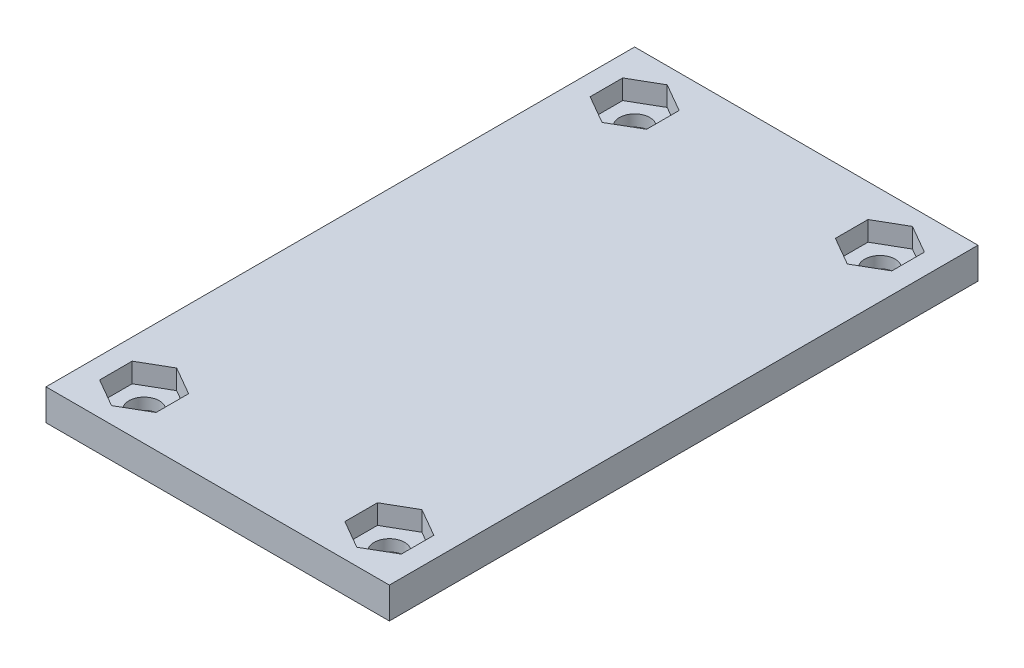
SolidWorks part; units mm, degrees
ref_plane "Front Plane" through (0, 0, 0) normal (0, 0, 1) x (1, 0, 0)
ref_plane "Top Plane" through (0, 0, 0) normal (0, 1, 0) x (1, 0, 0)
ref_plane "Right Plane" through (0, 0, 0) normal (1, 0, 0) x (0, 0, -1)
sketch "Sketch1" plane through (0, 0, 0) normal (0, 1, 0) x (1, 0, 0)
  line L1 (-12.5, -25) -> (12.5, -25) construction
  line L2 (-12.5, -25) -> (-12.5, 25) construction
  line L3 (-12.5, 25) -> (12.5, 25) construction
  line L4 (12.5, -25) -> (12.5, 25) construction
  line L5 (-12.5, -25) -> (12.5, 25) construction
  line L6 (-12.5, 25) -> (12.5, -25) construction
  line L7 (-17.5, -30) -> (17.5, -30)
  line L8 (-17.5, -30) -> (-17.5, 30)
  line L9 (-17.5, 30) -> (17.5, 30)
  line L10 (17.5, -30) -> (17.5, 30)
  line L11 (-17.5, -30) -> (17.5, 30) construction
  line L12 (-17.5, 30) -> (17.5, -30) construction
  line L13 (-12.5, 28.3198) -> (-15.375, 26.6599)
  line L14 (-15.375, 26.6599) -> (-15.375, 23.3401)
  line L15 (-15.375, 23.3401) -> (-12.5, 21.6802)
  line L16 (-12.5, 21.6802) -> (-9.625, 23.3401)
  line L17 (-9.625, 23.3401) -> (-9.625, 26.6599)
  line L18 (-9.625, 26.6599) -> (-12.5, 28.3198)
  line L19 (12.5, 28.3198) -> (9.625, 26.6599)
  line L20 (9.625, 26.6599) -> (9.625, 23.3401)
  line L21 (9.625, 23.3401) -> (12.5, 21.6802)
  line L22 (12.5, 21.6802) -> (15.375, 23.3401)
  line L23 (15.375, 23.3401) -> (15.375, 26.6599)
  line L24 (15.375, 26.6599) -> (12.5, 28.3198)
  line L25 (-12.5, -28.3198) -> (-9.625, -26.6599)
  line L26 (-9.625, -26.6599) -> (-9.625, -23.3401)
  line L27 (-9.625, -23.3401) -> (-12.5, -21.6802)
  line L28 (-12.5, -21.6802) -> (-15.375, -23.3401)
  line L29 (-15.375, -23.3401) -> (-15.375, -26.6599)
  line L30 (-15.375, -26.6599) -> (-12.5, -28.3198)
  line L31 (12.5, -21.6802) -> (9.625, -23.3401)
  line L32 (9.625, -23.3401) -> (9.625, -26.6599)
  line L33 (9.625, -26.6599) -> (12.5, -28.3198)
  line L34 (12.5, -28.3198) -> (15.375, -26.6599)
  line L35 (15.375, -26.6599) -> (15.375, -23.3401)
  line L36 (15.375, -23.3401) -> (12.5, -21.6802)
  circle A0 centre (-12.5, 25) radius 1.55
  circle A1 centre (12.5, 25) radius 1.55
  circle A2 centre (-12.5, -25) radius 1.55
  circle A3 centre (12.5, -25) radius 1.55
  circle A4 centre (-12.5, 25) radius 2.875 construction
  circle A5 centre (12.5, 25) radius 2.875 construction
  circle A6 centre (-12.5, -25) radius 2.875 construction
  circle A7 centre (12.5, -25) radius 2.875 construction
  point P0 (0, 0)
  point P10 (0, 0)
  dimension "D3" = 3.1
  dimension "D6" = 5.75
  dimension "D1" = 50
  dimension "D2" = 25
  dimension "D4" = 60
  dimension "D5" = 35
extrude "Boss-Extrude1" add sketch "Sketch1" along normal blind 3.175 contours L7 L10 L9 L8 L36 L35 L34 L33 L32 L31 L30 L29 L28 L27 L26 L25 L24 L23 L22 L21 L20 L19 L18 L17 L16 L15 L14 L13 | L17 L18 L13 L14 L15 L16 A0 | L23 L24 L19 L20 L21 L22 A1 | L35 L36 L31 L32 L33 L34 A3 | L29 L30 L25 L26 L27 L28 A2 region at (0, 0, 0) region at (-11.1064, 0, -27.4138) region at (13.8936, 0, -27.4138) region at (-13.8936, 0, 27.4138) region at (13.8936, 0, 22.5862)
extrude "Cut-Extrude1" cut sketch "Sketch1<3>" against normal blind 2 from surface contours L29 L30 L25 L26 L27 L28 A2 | L17 L18 L13 L14 L15 L16 A0 | L23 L24 L19 L20 L21 L22 A1 | L35 L36 L31 L32 L33 L34 A3 region at (-11.1064, 0, -27.4138) region at (13.8936, 0, -27.4138) region at (-13.8936, 0, 27.4138) region at (13.8936, 0, 22.5862) starting at face at (0, 3.175, 0)
sketch "Sketch1<3>" plane through (0, 0, 0) normal (0, 1, 0) x (1, 0, 0) same geometry as "Sketch1"
